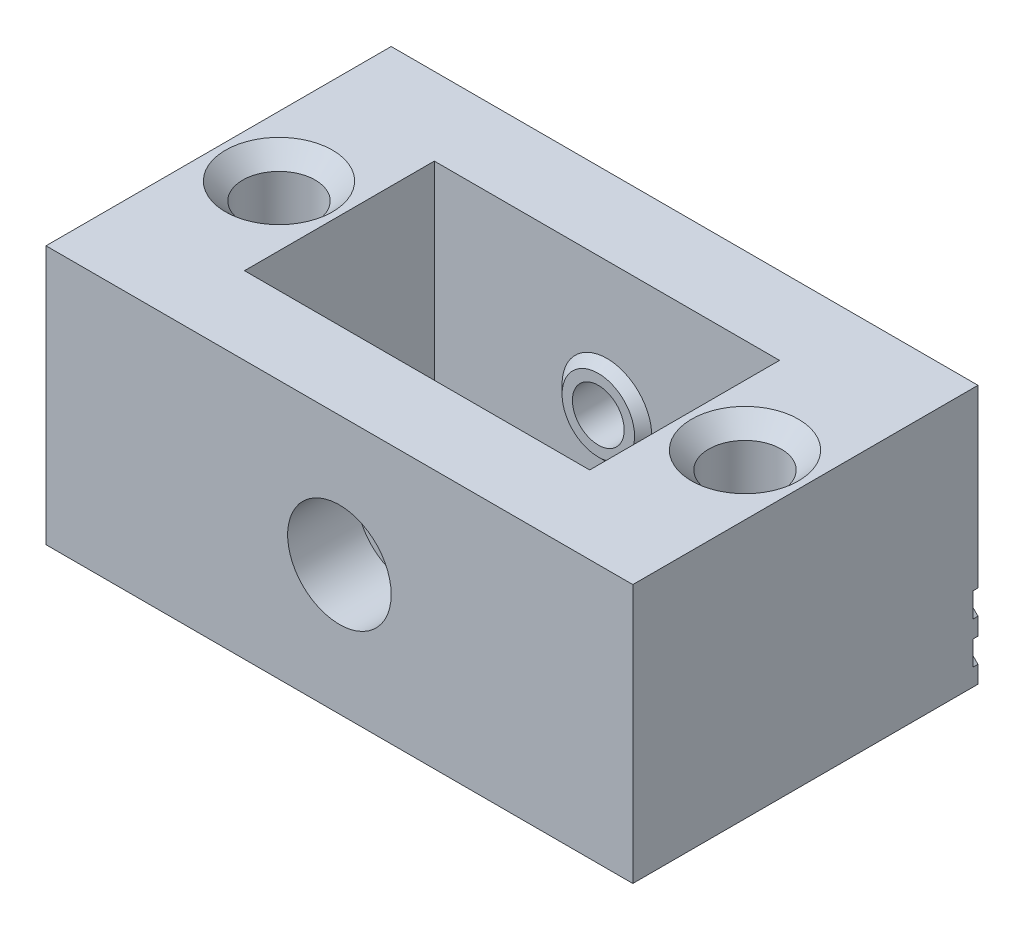
SolidWorks part; units mm, degrees
ref_plane "Front Plane" through (0, 0, 0) normal (0, 0, 1) x (1, 0, 0)
ref_plane "Top Plane" through (0, 0, 0) normal (0, 1, 0) x (1, 0, 0)
ref_plane "Right Plane" through (0, 0, 0) normal (1, 0, 0) x (0, 0, -1)
sketch "Sketch1" plane through (0, 0, 0) normal (0, 1, 0) x (1, 0, 0)
  line L1 (-17, -10) -> (17, -10)
  line L2 (-17, -10) -> (-17, 10)
  line L3 (-17, 10) -> (17, 10)
  line L4 (17, -10) -> (17, 10)
  line L5 (-17, -10) -> (17, 10) construction
  line L6 (-17, 10) -> (17, -10) construction
  point P0 (0, 0)
  dimension "D1" = 34
  dimension "D2" = 20
extrude "Boss-Extrude1" add sketch "Sketch1" along normal blind 15
sketch "Sketch3" plane through (0, 15, 0) normal (0, 1, 0) x (1, 0, 0)
  line L8 (-10, -5.5) -> (10, -5.5)
  line L9 (-10, -5.5) -> (-10, 5.5)
  line L10 (-10, 5.5) -> (10, 5.5)
  line L11 (10, -5.5) -> (10, 5.5)
  line L12 (-10, -5.5) -> (10, 5.5) construction
  line L13 (-10, 5.5) -> (10, -5.5) construction
  point P0 (0, 0)
  dimension "D1" = 11
  dimension "D2" = 20
extrude "Cut-Extrude1" cut sketch "Sketch3" against normal blind 20
sketch "Sketch8" plane through (0, 0, -10) normal (0, 0, -1) x (-1, 0, 0)
  line L0 (-17, 7.5) -> (17, 7.5) construction
  line L1 (17, 15) -> (17, 0) construction
  line L2 (-17, 15) -> (-17, 0) construction
  circle A0 centre (0, 7.5) radius 1.5
  dimension "D1" = 3
extrude "Cut-Extrude6" cut sketch "Sketch8" against normal through all
sketch "Sketch9" plane through (0, 0, 10) normal (0, 0, 1) x (1, 0, 0)
  circle A0 centre (0, 7.5) radius 3
  dimension "D1" = 6
extrude "Cut-Extrude7" cut sketch "Sketch9" against normal blind 4
sketch "Sketch11" plane through (0, 0, -5.5) normal (0, 0, 1) x (1, 0, 0)
  circle A0 centre (0, 7.5) radius 2.1
  circle A1 centre (0, 7.5) radius 1.5
  dimension "D1" = 0.6
extrude "Boss-Extrude2" add sketch "Sketch11" along normal blind 0.5
sketch "Sketch12" plane through (0, 0, 5.5) normal (0, 0, -1) x (-1, 0, 0)
  circle A0 centre (0, 7.5) radius 2.1
  circle A1 centre (0, 7.5) radius 1.5
  dimension "D1" = 0.6
extrude "Boss-Extrude3" add sketch "Sketch12" along normal blind 0.5
chamfer "Chamfer5" distance 0.5 angle 45 2 edges at (2.1, 7.5, 5.5) (-2.1, 7.5, -5.5)
sketch "Sketch13" plane through (0, 15, 0) normal (0, 1, 0) x (1, 0, 0)
  line L0 (-17, 0) -> (17, 0) construction
  line L1 (-17, 10) -> (-17, -10) construction
  line L2 (17, -10) -> (17, 10) construction
  circle A0 centre (-13.5, 0) radius 2.1
  circle A1 centre (13.5, 0) radius 2.1
  dimension "D1" = 4.2
  dimension "D2" = 3.5
  dimension "D3" = 3.5
extrude "Cut-Extrude8" cut sketch "Sketch13" against normal through all
chamfer "Chamfer6" distance 1 angle 45 2 edges at (13.5, 15, 2.1) (-13.5, 15, 2.1)
sketch "Sketch14" plane through (0, 0, -10) normal (0, 0, -1) x (-1, 0, 0)
  line L0 (17, 3.4142) -> (17, 4.8284)
  line L5 (16.2929, 4.1213) -> (17, 3.4142)
  line L6 (17, 4.8284) -> (16.2929, 4.1213)
  line L7 (-17, 2.4142) -> (-16.2929, 1.7071)
  line L12 (-17, 15) -> (-17, 0) construction
  line L13 (-16.2929, 1.7071) -> (-17, 1)
  line L14 (-17, 1) -> (-17, 2.4142)
  line L15 (-17, 0) -> (17, 0) construction
  line L16 (0, 15) -> (0, 0) construction
  line L17 (-17, 15) -> (17, 15) construction
  line L18 (16.2929, 1.7071) -> (17, 1)
  line L19 (17, 1) -> (17, 2.4142)
  line L20 (17, 2.4142) -> (16.2929, 1.7071)
  line L21 (-17, 4.8284) -> (-16.2929, 4.1213)
  line L22 (-16.2929, 4.1213) -> (-17, 3.4142)
  line L23 (-17, 3.4142) -> (-17, 4.8284)
  dimension "D1" = 45
  dimension "D2" = 1
  dimension "D3" = 1
  dimension "D4" = 1
  dimension "D5" = 1
  dimension "D6" = 45
extrude "Cut-Extrude9" cut sketch "Sketch14" against normal blind 0.3
